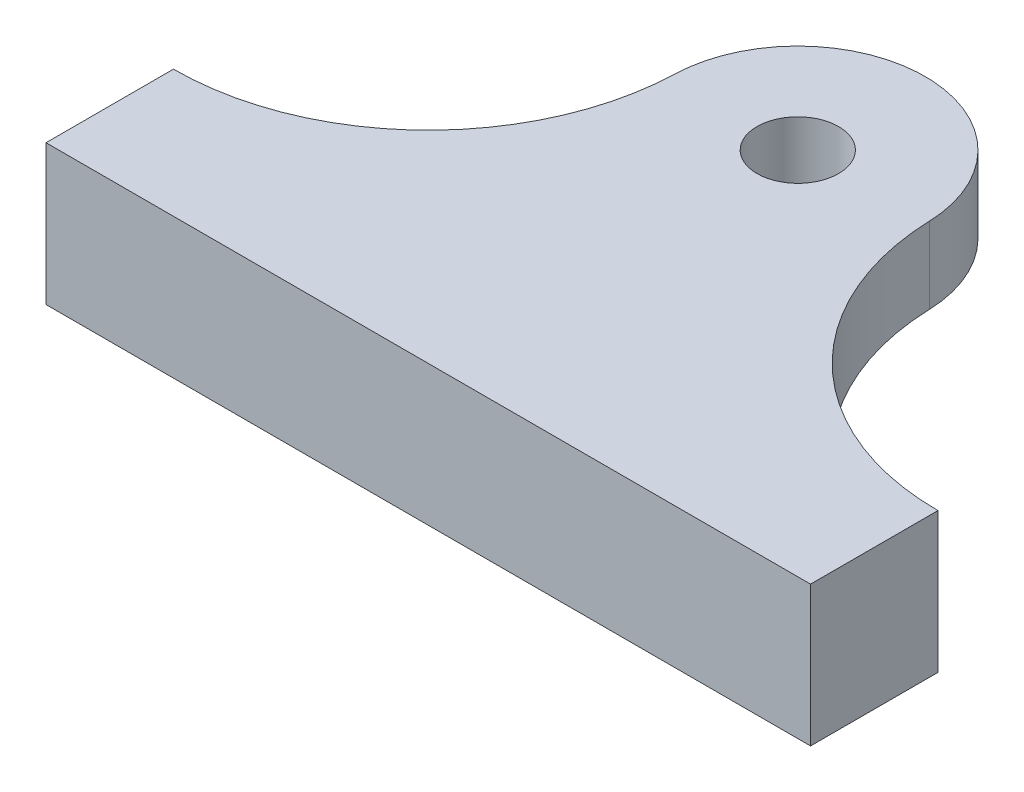
SolidWorks part; units mm, degrees
ref_plane "前视基准面" through (0, 0, 0) normal (0, 0, 1) x (1, 0, 0)
ref_plane "上视基准面" through (0, 0, 0) normal (0, 1, 0) x (1, 0, 0)
ref_plane "右视基准面" through (0, 0, 0) normal (1, 0, 0) x (0, 0, -1)
sketch "草图1" plane through (0, 0, 0) normal (0, 1, 0) x (1, 0, 0)
  line L0 (-5, 0) -> (-5, -9.5)
  line L1 (-5, -9.5) -> (5, -9.5)
  line L2 (5, -9.5) -> (5, 0)
  circle A0 centre (0, 0) radius 1.6
  arc A1 (5, 0) -> (-5, 0) centre (0, 0) ccw
  dimension "D1" = 3.2
  dimension "D2" = 10
  dimension "D3" = 9.5
extrude "凸台-拉伸1" add sketch "草图1" along normal blind 3
sketch "草图2" plane through (0, 3, 0) normal (0, 1, 0) x (1, 0, 0)
  line L0 (-5, -9.5) -> (5, -9.5) construction
  line L1 (-15, -9.5) -> (15, -9.5)
  line L2 (-15, -9.5) -> (-15, -14.5)
  line L3 (-15, -14.5) -> (15, -14.5)
  line L4 (15, -9.5) -> (15, -14.5)
  line L5 (-15, -9.5) -> (15, -14.5) construction
  line L6 (-15, -14.5) -> (15, -9.5) construction
  line L7 (0, 0) -> (0, -9.5) construction
  point P4 (0, -12)
  dimension "D1" = 30
  dimension "D2" = 5
extrude "凸台-拉伸2" add sketch "草图2" against normal blind 5.5
fillet "圆角1" radius 10 2 edges at (-5, 1.5, 9.5) (5, 1.5, 9.5)
